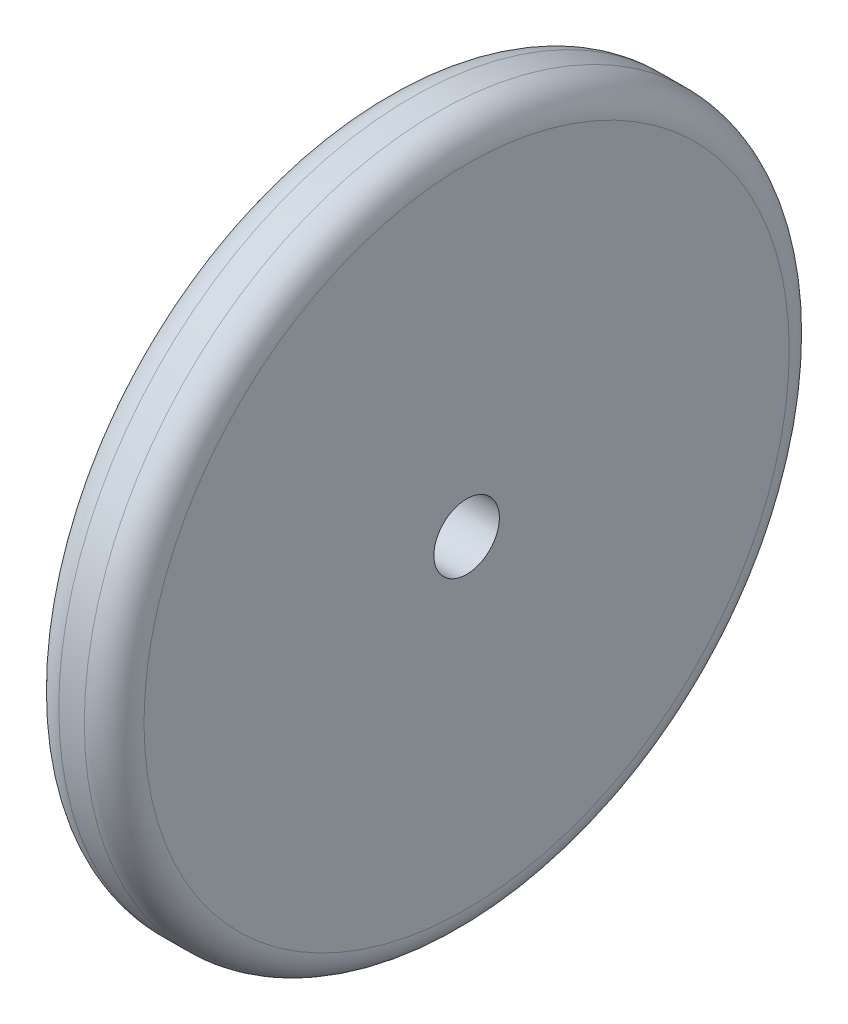
SolidWorks part; units mm, degrees
material "Default"
ref_plane "Top" through (0, 0, 0) normal (0, 0, 1) x (1, 0, 0)
ref_plane "Right" through (0, 0, 0) normal (0, 1, 0) x (1, 0, 0)
ref_plane "Front" through (0, 0, 0) normal (1, 0, 0) x (0, 0, -1)
ref_axis "Axis1" through (-88.1547, -99.414, 18.1528) along (1, 0, 0)
ref_plane "Plane1" through (0, 0, 18.1528) normal (0, 0, -1) x (-1, 0, 0)
sketch "Sketch2" plane through (0, 0, 18.1528) normal (0, 0, -1) x (-1, 0, 0)
  line L0 (88.1547, -99.414) -> (66.2441, -99.414) construction
  line L1 (88.1547, -101.364) -> (88.1547, -97.464) construction
  line L2 (72.8316, -99.414) -> (72.8316, -94.2869) construction
  line L3 (79.3565, -99.414) -> (79.3565, -91.9148) construction
  line L4 (72.8316, -98.744) -> (79.3565, -98.744) construction
  line L5 (76.094, -98.744) -> (76.094, -90.8339) construction
  line L6 (73.554, -97.464) -> (73.554, -78.414)
  line L7 (88.1547, -97.464) -> (55.1347, -97.464) construction
  line L8 (73.554, -78.414) -> (78.634, -78.414)
  line L9 (78.634, -97.464) -> (78.634, -78.414)
  line L10 (73.554, -97.464) -> (78.634, -97.464)
  point P22 (76.094, -78.414)
  dimension "D1" = 19.05
  dimension "D2" = 2.54
revolve "Revolve1" add sketch "Sketch2" angle 360 about L0
fillet "Fillet1" radius 1.778 2 edges at (-78.634, -99.414, 39.1528) (-73.554, -99.414, 39.1528)
